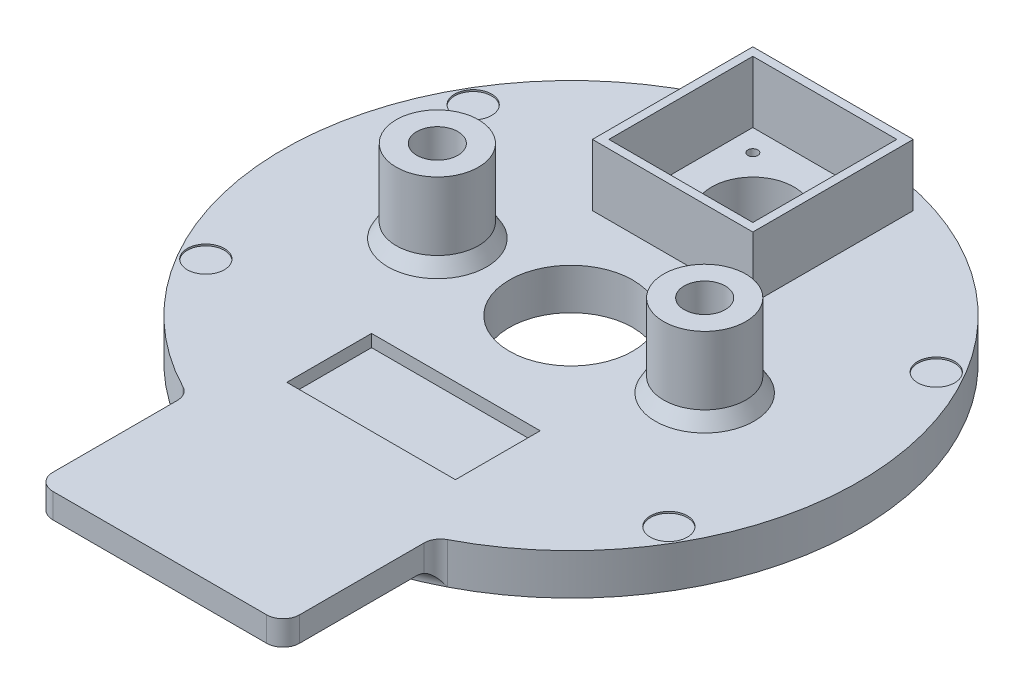
SolidWorks part; units mm, degrees
ref_plane "Front Plane" through (0, 0, 0) normal (0, 0, 1) x (1, 0, 0)
ref_plane "Top Plane" through (0, 0, 0) normal (0, 1, 0) x (1, 0, 0)
ref_plane "Right Plane" through (0, 0, 0) normal (1, 0, 0) x (0, 0, -1)
sketch "Sketch1" plane through (0, 0, 0) normal (0, 1, 0) x (1, 0, 0)
  circle A0 centre (0, 0) radius 88.9
  dimension "6" = 177.8
extrude "Boss-Extrude1" add sketch "Sketch1" along normal blind 12.7
sketch "Sketch9" plane through (0, 12.7, 0) normal (0, 1, 0) x (1, 0, 0)
  line L5 (-24.765, 80.899) -> (-24.765, 31.369)
  line L7 (-22.225, 78.359) -> (22.225, 78.359)
  line L9 (-22.225, 78.359) -> (-22.225, 33.909)
  line L10 (0, 56.134) -> (0, 0) construction
  line L11 (-22.225, 33.909) -> (22.225, 33.909)
  line L37 (22.225, 78.359) -> (22.225, 33.909)
  line L38 (-22.225, 78.359) -> (22.225, 33.909) construction
  line L39 (-22.225, 33.909) -> (22.225, 78.359) construction
  line L40 (-24.765, 31.369) -> (24.765, 31.369)
  line L41 (24.765, 80.899) -> (24.765, 31.369)
  line L42 (-24.765, 80.899) -> (24.765, 80.899)
  dimension "D1" = 44.45
  dimension "D2" = 44.45
  dimension "D3" = 56.134
  dimension "D4" = 2.54
extrude "Boss-Extrude2" add sketch "Sketch9" along normal blind 19.05
sketch "Sketch10" plane through (0, 12.7, 0) normal (0, 1, 0) x (1, 0, 0)
  line L1 (71.4904, 41.275) -> (-71.4904, 41.275) construction
  line L2 (71.4904, 41.275) -> (71.4904, -41.275) construction
  line L3 (71.4904, -41.275) -> (-71.4904, -41.275) construction
  line L4 (-71.4904, 41.275) -> (-71.4904, -41.275) construction
  line L5 (71.4904, 41.275) -> (-71.4904, -41.275) construction
  line L6 (71.4904, -41.275) -> (-71.4904, 41.275) construction
  circle A0 centre (0, 0) radius 82.55 construction
  circle A1 centre (-71.4904, -41.275) radius 5.715
  circle A2 centre (-71.4904, 41.275) radius 5.715
  circle A3 centre (71.4904, 41.275) radius 5.715
  circle A4 centre (71.4904, -41.275) radius 5.715
  point P0 (0, 0)
  dimension "D1" = 165.1
  dimension "D3" = 11.43
  dimension "D2" = 30
extrude "Cut-Extrude7" cut sketch "Sketch10" against normal blind 0.508
sketch "Sketch12" [suppressed] plane through (0, 7.62, 0) normal (0, 1, 0) x (1, 0, 0)
  circle A0 centre (-58.3726, 48.9804) radius 1.5
  circle A1 centre (58.3726, 48.9804) radius 1.5
  circle A2 centre (-58.3726, -48.9804) radius 1.5
  circle A3 centre (58.3726, -48.9804) radius 1.5
  dimension "D1" = 3
extrude "Cut-Extrude9" [suppressed] cut sketch "Sketch12" against normal up to surface (7.62 mm away)
sketch "Sketch13" [suppressed] plane through (0, 0, 0) normal (0, -1, 0) x (1, 0, 0)
  circle A1 centre (-58.3726, 48.9804) radius 1.905
  circle A2 centre (-58.3726, 48.9804) radius 1.905
  circle A3 centre (58.3726, 48.9804) radius 1.905
  circle A4 centre (58.3726, 48.9804) radius 1.905
  circle A5 centre (58.3726, -48.9804) radius 1.905
  circle A6 centre (58.3726, -48.9804) radius 1.905
  circle A7 centre (-58.3726, -48.9804) radius 1.905
  circle A8 centre (-58.3726, -48.9804) radius 1.905
  dimension "D1" = 0
  dimension "D2" = 0
  dimension "D3" = 0
  dimension "D4" = 0
extrude "Cut-Extrude10" [suppressed] cut sketch "Sketch13" against normal blind 12.7
sketch "Sketch14" plane through (0, 0, 0) normal (0, -1, 0) x (1, 0, 0)
  circle A0 centre (0, 0) radius 19.05
  dimension "D1" = 38.1
extrude "Cut-Extrude11" cut sketch "Sketch14" against normal up to surface (12.7 mm away) up to face at (71.4904, 12.7, 46.99)
sketch "Sketch15" plane through (0, 12.7, 0) normal (0, 1, 0) x (1, 0, 0)
  line L0 (-41.275, 0) -> (41.275, 0) construction
  circle A0 centre (41.275, 0) radius 6.35
  circle A1 centre (-41.275, 0) radius 6.35
  circle A2 centre (-41.275, 0) radius 12.7
  circle A3 centre (41.275, 0) radius 12.7
  dimension "D1" = 6.35
  dimension "D2" = 82.55
  dimension "D3" = 12.7
extrude "Boss-Extrude3" add sketch "Sketch15" along normal blind 25.4
sketch "Sketch16" plane through (0, 12.7, 0) normal (0, 1, 0) x (1, 0, 0)
  circle A0 centre (41.275, 0) radius 6.35 construction
  circle A1 centre (-41.275, 0) radius 6.35 construction
  circle A2 centre (41.275, 0) radius 6.35
  circle A3 centre (-41.275, 0) radius 6.35
extrude "Cut-Extrude12" cut sketch "Sketch16" against normal blind 12.7
sketch "Sketch17" plane through (0, 0, 0) normal (0, -1, 0) x (1, 0, 0)
  circle A0 centre (41.275, 0) radius 9.525
  circle A1 centre (-41.275, 0) radius 9.525
  dimension "D1" = 19.05
  dimension "D2" = 19.05
extrude "Cut-Extrude13" cut sketch "Sketch17" against normal blind 25.4
sketch "Sketch18" plane through (0, 12.7, 0) normal (0, 1, 0) x (1, 0, 0)
  circle A1 centre (0, 0) radius 19.05 construction
  circle A2 centre (0, 0) radius 19.05
  circle A3 centre (0, 0) radius 24.13
  dimension "D1" = 5.08
extrude "Boss-Extrude4" [suppressed] add sketch "Sketch18" along normal blind 6.35
chamfer "Chamfer2" distance 2.54 angle 60 2 edges at (41.275, 12.7, 12.7) (-41.275, 12.7, 12.7) first distance on face at (41.275, 12.7, 12.7)
sketch "Sketch19" plane through (0, 12.7, 0) normal (0, 1, 0) x (1, 0, 0)
  line L0 (22.225, 56.134) -> (-22.225, 56.134) construction
  line L1 (22.225, 33.909) -> (22.225, 78.359) construction
  line L2 (0, 88.9) -> (0, 0) construction
  line L4 (-22.225, 78.359) -> (-22.225, 33.909) construction
  line L5 (-15.494, 71.628) -> (15.494, 71.628) construction
  line L6 (-15.494, 71.628) -> (-15.494, 40.64) construction
  line L7 (-15.494, 40.64) -> (15.494, 40.64) construction
  line L8 (15.494, 71.628) -> (15.494, 40.64) construction
  line L9 (-15.494, 71.628) -> (15.494, 40.64) construction
  line L10 (-15.494, 40.64) -> (15.494, 71.628) construction
  circle A0 centre (0, 56.134) radius 12.7
  circle A1 centre (15.494, 71.628) radius 1.524
  circle A2 centre (15.494, 40.64) radius 1.524
  circle A3 centre (-15.494, 40.64) radius 1.524
  circle A4 centre (-15.494, 71.628) radius 1.524
  circle A5 centre (0, 0) radius 88.9 construction
  dimension "D2" = 25.4
  dimension "D5" = 3.048
  dimension "D3" = 30.988
  dimension "D4" = 30.988
extrude "Cut-Extrude14" cut sketch "Sketch19" against normal up to surface (12.7 mm away) up to face at (41.275, 0, -9.525)
sketch "Sketch20" [suppressed] plane through (0, 12.7, 0) normal (0, 1, 0) x (1, 0, 0)
  circle A0 centre (-71.4904, -41.275) radius 4.191 construction
  circle A1 centre (71.4904, -41.275) radius 4.191 construction
  circle A2 centre (71.4904, 41.275) radius 4.191 construction
  circle A3 centre (-71.4904, 41.275) radius 4.191 construction
  circle A4 centre (-71.4904, -41.275) radius 4.191
  circle A5 centre (71.4904, -41.275) radius 4.191
  circle A6 centre (71.4904, 41.275) radius 4.191
  circle A7 centre (-71.4904, 41.275) radius 4.191
  circle A8 centre (-71.4904, 41.275) radius 5.461
  circle A9 centre (71.4904, 41.275) radius 5.461
  circle A10 centre (71.4904, -41.275) radius 5.461
  circle A11 centre (-71.4904, -41.275) radius 5.461
  dimension "D1" = 1.27
fillet "Fillet1" [suppressed] radius 6.35
sketch "Sketch21" plane through (0, 0, 0) normal (0, -1, 0) x (1, 0, 0)
  circle A0 centre (-15.494, -71.628) radius 1.524 construction
  circle A1 centre (15.494, -71.628) radius 1.524 construction
  circle A2 centre (15.494, -40.64) radius 1.524 construction
  circle A3 centre (-15.494, -40.64) radius 1.524 construction
  circle A4 centre (-15.494, -71.628) radius 1.524 construction
  circle A5 centre (15.494, -71.628) radius 1.524 construction
  circle A6 centre (15.494, -40.64) radius 1.524 construction
  circle A7 centre (-15.494, -40.64) radius 1.524 construction
  circle A8 centre (-15.494, -71.628) radius 4.064
  circle A9 centre (15.494, -71.628) radius 4.064
  circle A10 centre (15.494, -40.64) radius 4.064
  circle A11 centre (-15.494, -40.64) radius 4.064
  circle A12 centre (-71.4904, 41.275) radius 5.715 construction
  circle A13 centre (-71.4904, 41.275) radius 5.715
  circle A14 centre (71.4904, 41.275) radius 5.715 construction
  circle A15 centre (71.4904, 41.275) radius 5.715
  circle A16 centre (71.4904, -41.275) radius 5.715 construction
  circle A17 centre (71.4904, -41.275) radius 5.715
  circle A18 centre (-71.4904, -41.275) radius 5.715 construction
  circle A19 centre (-71.4904, -41.275) radius 5.715
  dimension "D1" = 2.54
extrude "Cut-Extrude15" cut sketch "Sketch21" against normal blind 5.08
ref_plane "Plane1" through (0, 12.7, 0) normal (0, 1, 0) x (1, 0, 0)
sketch "Sketch22" plane through (0, 12.7, 0) normal (0, 1, 0) x (1, 0, 0)
  line L0 (0, -19.05) -> (0, -88.9) construction
  line L2 (-26.035, -35.56) -> (26.035, -35.56)
  line L3 (-26.035, -35.56) -> (-26.035, -61.722)
  line L4 (-26.035, -61.722) -> (26.035, -61.722)
  line L5 (26.035, -35.56) -> (26.035, -61.722)
  line L6 (-26.035, -35.56) -> (26.035, -61.722) construction
  line L7 (-26.035, -61.722) -> (26.035, -35.56) construction
  circle A0 centre (0, 0) radius 19.05 construction
  circle A1 centre (0, 0) radius 88.9 construction
  point P7 (0, -48.641)
  dimension "D1" = 52.07
  dimension "D2" = 26.162
  dimension "D3" = 35.56
extrude "Cut-Extrude17" cut sketch "Sketch22" against normal blind 3.81
sketch "Sketch23" plane through (0, 12.7, 0) normal (0, 1, 0) x (1, 0, 0)
  line L0 (0, 0) -> (0, -88.9) construction
  line L1 (-38.1, -80.3219) -> (-38.1, -127)
  line L2 (-38.1, -127) -> (38.1, -127)
  line L3 (38.1, -80.3219) -> (38.1, -127)
  circle A0 centre (0, 0) radius 88.9 construction
  arc A1 (-38.1, -80.3219) -> (38.1, -80.3219) centre (0, 0) ccw
  point P13 (0, -127)
  dimension "D1" = 38.1
  dimension "D2" = 38.1
extrude "Boss-Extrude5" add sketch "Sketch23" against normal blind 7.62
fillet "Fillet2" radius 5.08 5 edges at (38.1, 8.89, 127) (-38.1, 8.89, 127) (-38.1, 8.89, 80.3219) (0, 5.08, 88.9) (38.1, 8.89, 80.3219)
equation "\"25nn\"=0.497491"
